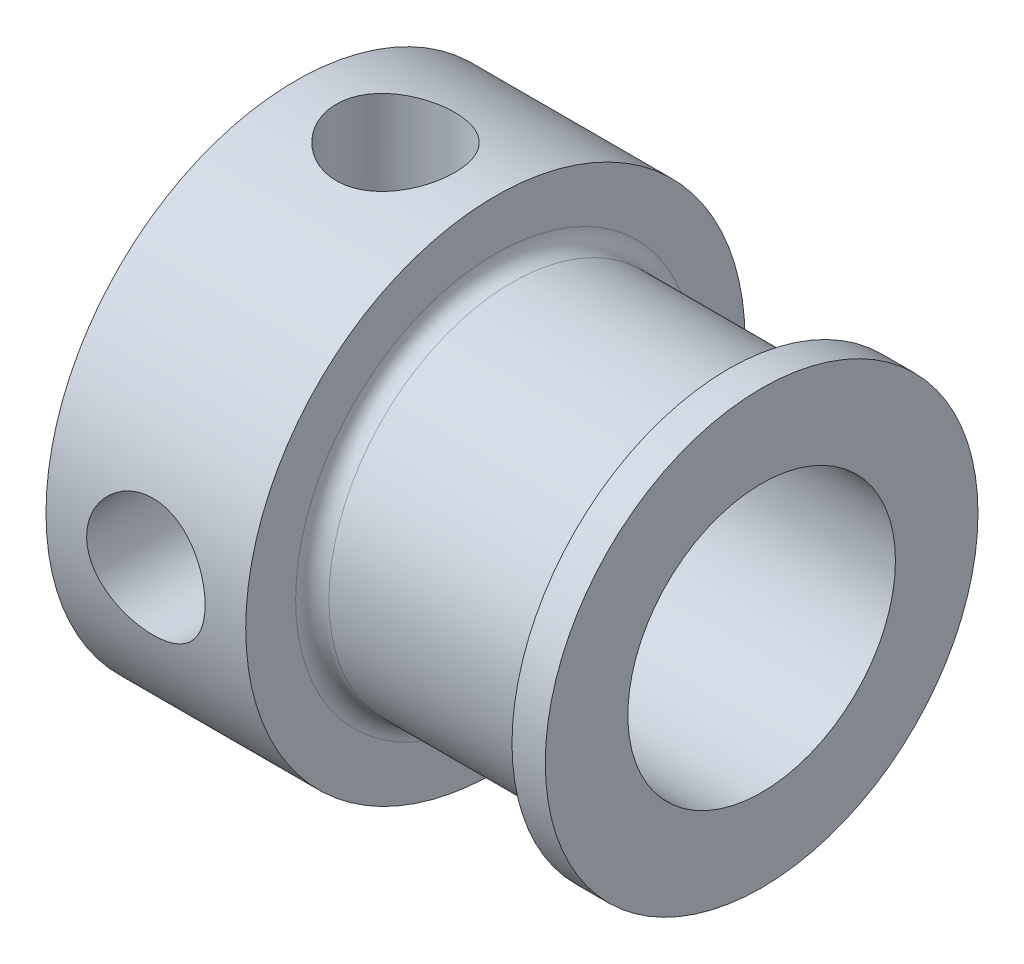
SolidWorks part; units mm, degrees
material "Cast Alloy Steel"
ref_plane "Front Plane" through (0, 0, 0) normal (0, 0, 1) x (1, 0, 0)
ref_plane "Top Plane" through (0, 0, 0) normal (0, 1, 0) x (1, 0, 0)
ref_plane "Right Plane" through (0, 0, 0) normal (1, 0, 0) x (0, 0, -1)
sketch "Sketch1" plane through (0, 0, 0) normal (1, 0, 0) x (0, 0, -1)
  circle A0 centre (0, 0) radius 4.7625
  circle A1 centre (0, 0) radius 2.5527
  dimension "D1" = 5.1054
  dimension "D2" = 9.525
extrude "Boss-Extrude1" add sketch "Sketch1" along normal blind 8.89
sketch "Sketch2" plane through (0, 0, 0) normal (0, 0, 1) x (1, 0, 0)
  line L0 (8.89, 4.7625) -> (0, 4.7625) construction
  line L1 (3.81, 4.7625) -> (8.89, 4.7625)
  line L2 (3.81, 4.7625) -> (3.81, 3.4925)
  line L3 (3.81, 3.4925) -> (8.255, 3.4925)
  line L4 (8.255, 3.4925) -> (8.255, 4.1275)
  line L5 (0, 4.7625) -> (0, -4.7625) construction
  line L6 (8.255, 4.1275) -> (8.89, 4.1275)
  line L8 (8.89, 4.1275) -> (8.89, 4.7625)
  line L9 (8.89, -2.5527) -> (8.89, 2.5527) construction
  dimension "D1" = 3.81
  dimension "D2" = 0.635
  dimension "D3" = 1.27
  dimension "D4" = 0.635
ref_axis "Axis1" through (8.89, 0, 0) along (-1, 0, 0)
revolve "Cut-Revolve1" cut sketch "Sketch2" angle 360 about axis through (8.89, 0, 0) along (-1, 0, 0)
sketch "Sketch7" plane through (0, 0, 0) normal (0, 1, 0) x (1, 0, 0)
  line L0 (8.89, 0) -> (0, 0) construction
  line L1 (0, 4.7625) -> (0, -4.7625) construction
  circle A0 centre (1.905, 3.81) radius 0.3969
  dimension "D1" = 0.7937
  dimension "D2" = 3.81
  dimension "D3" = 1.905
extrude "Cut-Extrude1" cut sketch "Sketch7" against normal through all and the other way through all
hole_wizard "ShaftSetScrew" positions "Sketch4" profile "Sketch3" tap size "#4-40" standard "ANSI Inch" end condition up to next
sketch "Sketch4" plane through (0, 0, 0) normal (0, 0, 1) x (1, 0, 0)
  line L0 (8.89, 0) -> (0, 0) construction
  line L1 (0, 4.7625) -> (0, -4.7625) construction
  point P0 (1.905, 0)
  dimension "D1" = 1.905
sketch "Sketch3" plane through (1.905, 0, 0) normal (1, 0, 0) x (0, 1, 0)
  line L0 (0, 0) -> (0, 4.7635)
  line L1 (0, 4.7635) -> (1.1303, 4.7635)
  line L2 (1.1303, 4.7635) -> (1.1303, 0)
  line L5 (1.1303, 0) -> (0, 0)
  line L11 (0, -6.35) -> (0, 107.95) construction
  dimension "Thread Major Dia." = 2.2606
  dimension "Thru Tap Drill Depth" = 4.7635
fillet "Fillet2" radius 0.3175 2 edges at (3.81, 0, -3.4925) (8.255, 0, -3.4925)
pattern_circular "CirPattern1" count 4 every 90 about axis through (8.89, 0, 0) along (-1, 0, 0) skipping 2 of "ShaftSetScrew"
